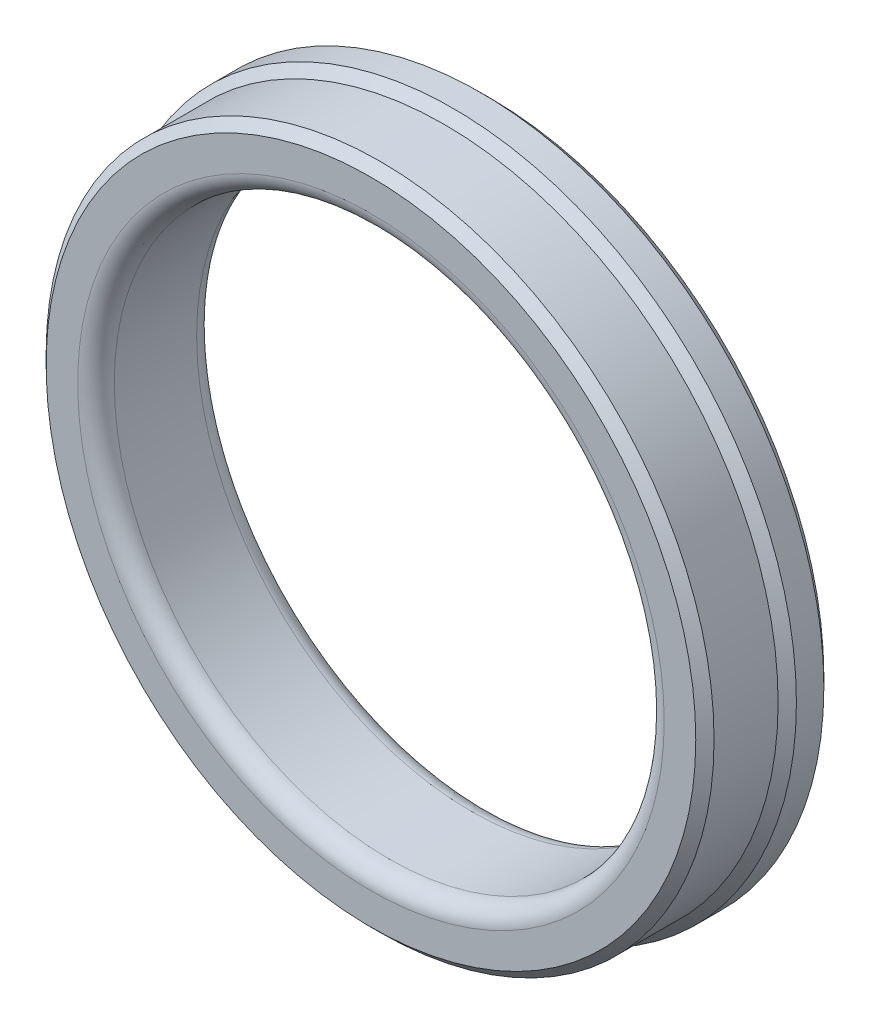
SolidWorks part; units mm, degrees
ref_plane "Front Plane" through (0, 0, 0) normal (0, 0, 1) x (1, 0, 0)
ref_plane "Top Plane" through (0, 0, 0) normal (0, 1, 0) x (1, 0, 0)
ref_plane "Right Plane" through (0, 0, 0) normal (1, 0, 0) x (0, 0, -1)
sketch "Sketch1" plane through (0, 0, 0) normal (0, 0, 1) x (1, 0, 0)
  circle A0 centre (0, 0) radius 37.5
  circle A1 centre (0, 0) radius 30.05
  dimension "D1" = 75
  dimension "D2" = 60.1
extrude "Boss-Extrude1" add sketch "Sketch1" along normal blind 5
sketch "Sketch2" plane through (0, 0, 5) normal (0, 0, 1) x (1, 0, 0)
  circle A0 centre (0, 0) radius 30.05 construction
  circle A1 centre (0, 0) radius 30.05
  circle A2 centre (0, 0) radius 36.5
  dimension "D1" = 73
extrude "Boss-Extrude2" add sketch "Sketch2" along normal blind 8
chamfer "Chamfer1" distance 1 angle 45 3 edges at (37.5, 0, 5) (36.5, 0, 13) (37.5, 0, 0)
fillet "Fillet1" radius 2 2 edges at (30.05, 0, 0) (30.05, 0, 13)
